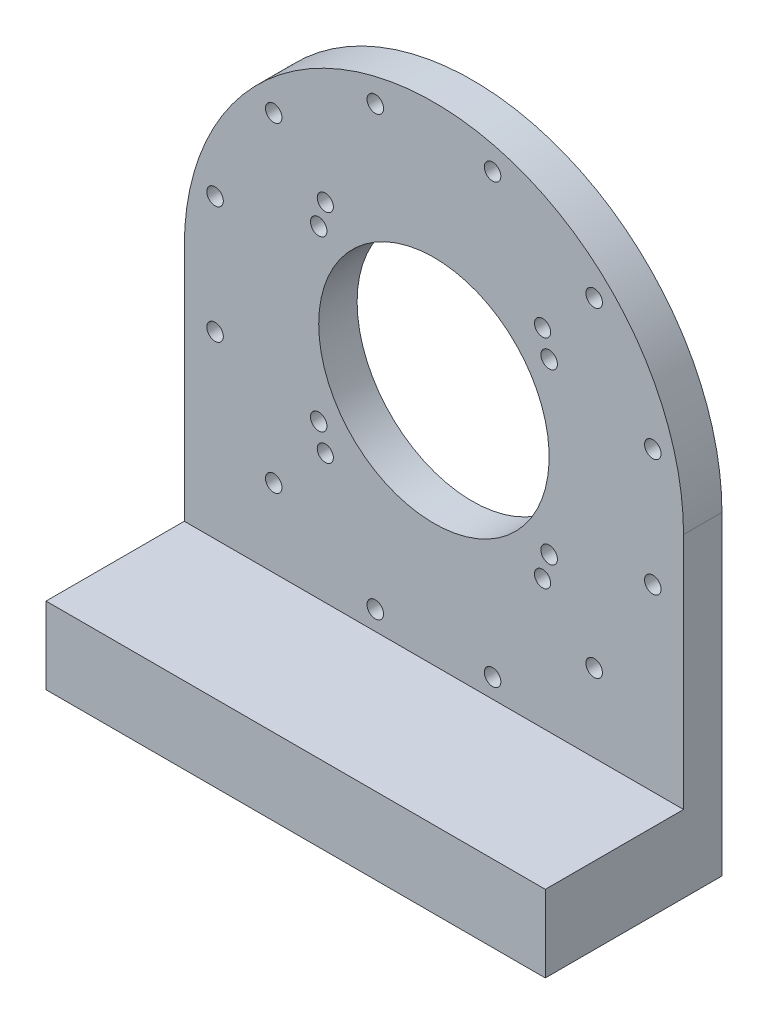
SolidWorks part; units mm, degrees
ref_plane "Front Plane" through (0, 0, 0) normal (0, 0, 1) x (1, 0, 0)
ref_plane "Top Plane" through (0, 0, 0) normal (0, 1, 0) x (1, 0, 0)
ref_plane "Right Plane" through (0, 0, 0) normal (1, 0, 0) x (0, 0, -1)
sketch "Sketch1" plane through (0, 0, -97.5071) normal (0, 0, -1) x (-1, 0, 0)
  line L0 (-154.0728, 47.2587) -> (-154.0728, -14.7413)
  line L1 (-24.0728, 47.2587) -> (-24.0728, -14.7413)
  line L2 (-154.0728, -14.7413) -> (-24.0728, -14.7413)
  line L4 (-154.0728, -14.7413) -> (-24.0728, -14.7413)
  line L5 (-154.0728, -14.7413) -> (-154.0728, -34.7413)
  line L6 (-154.0728, -34.7413) -> (-24.0728, -34.7413)
  line L7 (-24.0728, -14.7413) -> (-24.0728, -34.7413)
  line L9 (-24.0728, -14.7413) -> (-24.0728, -34.7413)
  line L13 (-154.0728, -34.7413) -> (-154.0728, -14.7413)
  arc A0 (-24.0728, 47.2587) -> (-154.0728, 47.2587) centre (-89.0728, 47.2587) ccw
  line M11 (-116.0728, 53.2587) -> (-116.0728, 41.2587)
  line M12 (-116.0728, 41.2587) -> (-149.777, 41.2587)
  arc M13 (-149.777, 41.2587) -> (-149.777, 53.2587) centre (-89.0728, 47.2587) ccw
  line M14 (-149.777, 53.2587) -> (-116.0728, 53.2587)
  circle M15 centre (-117.3571, 18.9744) radius 2.1
  circle M16 centre (-60.7885, 18.9744) radius 2.1
  circle M17 centre (-60.7885, 75.543) radius 2.1
  circle M18 centre (-117.3571, 75.543) radius 2.1
  circle M19 centre (-104.3431, 104.2483) radius 1.575
  circle M20 centre (-146.0624, 62.529) radius 1.575
  circle M21 centre (-130.7921, 5.5394) radius 1.575
  circle M22 centre (-73.8025, -9.7309) radius 1.575
  circle M23 centre (-32.0832, 31.9884) radius 1.575
  circle M24 centre (-32.0832, 62.529) radius 1.575
  circle M25 centre (-47.3535, 88.978) radius 1.575
  circle M26 centre (-47.3535, 5.5394) radius 1.575
  circle M27 centre (-104.3431, -9.7309) radius 1.575
  circle M28 centre (-146.0624, 31.9884) radius 1.575
  circle M29 centre (-130.7921, 88.978) radius 1.575
  circle M30 centre (-73.8025, 104.2483) radius 1.575
  circle M31 centre (-89.0728, 47.2587) radius 15
  dimension "D3" = 65
  dimension "D1" = 20
  dimension "D2" = 62
  dimension "D4" = 130
extrude "Boss-Extrude1" add sketch "Sketch1" along normal blind 10 contours L1 A0 L0 L2 M11 M14 M13 M12 | L7 L2 L5 L6 | M14 M11 M12 M13 M15 M17 M19 M21 M23 M25 M27 M29 M31 M30 M28 M26 M24 M22 M20 M18 M16 region at (89.0728, 110.4413, -97.5071) region at (89.0728, -24.7413, -97.5071) region at (132.9249, 54.982, -97.5071)
extrude "Boss-Extrude2" add sketch "Sketch1<3>" against normal blind 36 contours L7 L2 L5 L6 region at (89.0728, -24.7413, -97.5071)
sketch "Sketch1<3>" plane through (0, 0, -97.5071) normal (0, 0, -1) x (-1, 0, 0) same geometry as "Sketch1"
sketch "Sketch2" plane through (0, 0, -107.5071) normal (0, 0, -1) x (-1, 0, 0)
  circle A0 centre (-89.0728, 47.2587) radius 30
  dimension "D1" = 60
extrude "Cut-Extrude1" cut sketch "Sketch2" against normal blind 36
sketch "Sketch4" plane through (0, 0, -107.5071) normal (0, 0, -1) x (-1, 0, 0)
  circle A0 centre (-73.8025, 104.2483) radius 2.15
  circle A1 centre (-47.3535, 88.978) radius 2.15
  circle A2 centre (-32.0832, 62.529) radius 2.15
  circle A3 centre (-32.0832, 31.9884) radius 2.15
  circle A4 centre (-47.3535, 5.5394) radius 2.15
  circle A5 centre (-73.8025, -9.7309) radius 2.15
  circle A6 centre (-104.3431, -9.7309) radius 2.15
  circle A7 centre (-130.7921, 5.5394) radius 2.15
  circle A8 centre (-146.0624, 31.9884) radius 2.15
  circle A9 centre (-146.0624, 62.529) radius 2.15
  circle A10 centre (-130.7921, 88.978) radius 2.15
  circle A11 centre (-104.3431, 104.2483) radius 2.15
  point P28 (-89.0728, 47.2587)
  dimension "D1" = 4.3
  dimension "D2" = 12
extrude "Cut-Extrude2" cut sketch "Sketch4" against normal through all
sketch "Sketch5" plane through (0, 0, -107.5071) normal (0, 0, -1) x (-1, 0, 0)
  line L1 (-59.0728, 25.2587) -> (-119.0728, 25.2587) construction
  line L2 (-59.0728, 25.2587) -> (-59.0728, 69.2587) construction
  line L3 (-59.0728, 69.2587) -> (-119.0728, 69.2587) construction
  line L4 (-119.0728, 25.2587) -> (-119.0728, 69.2587) construction
  line L5 (-59.0728, 25.2587) -> (-119.0728, 69.2587) construction
  line L6 (-59.0728, 69.2587) -> (-119.0728, 25.2587) construction
  circle A0 centre (-119.0728, 69.2587) radius 2.15
  circle A1 centre (-59.0728, 69.2587) radius 2.15
  circle A2 centre (-59.0728, 25.2587) radius 2.15
  circle A3 centre (-119.0728, 25.2587) radius 2.15
  point P0 (-89.0728, 47.2587)
  dimension "D3" = 4.3
  dimension "D4" = 4.3
  dimension "D5" = 4.3
  dimension "D6" = 4.3
  dimension "D1" = 60
  dimension "D2" = 44
extrude "Cut-Extrude3" cut sketch "Sketch5" against normal through all
equation "\"helloi\"= 123"
